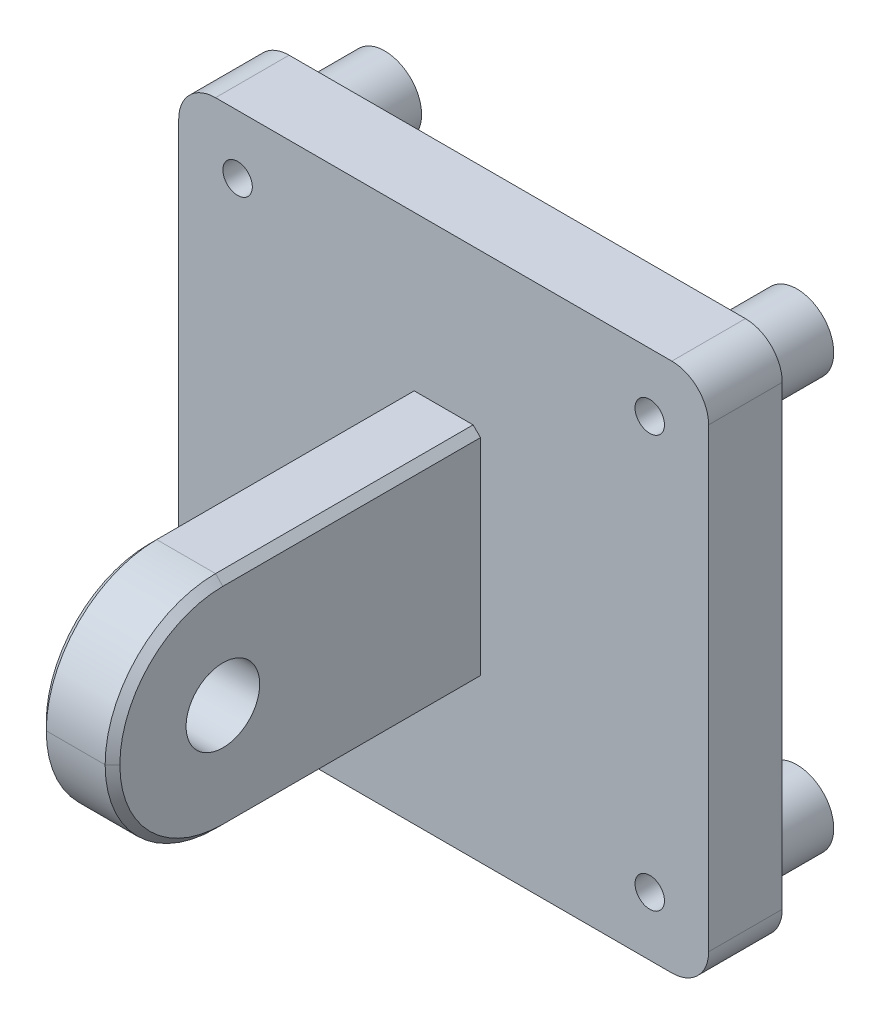
SolidWorks part; units mm, degrees
ref_plane "Front Plane" through (0, 0, 0) normal (0, 0, 1) x (1, 0, 0)
ref_plane "Top Plane" through (0, 0, 0) normal (0, 1, 0) x (1, 0, 0)
ref_plane "Right Plane" through (0, 0, 0) normal (1, 0, 0) x (0, 0, -1)
sketch "Sketch1" plane through (0, 0, 0) normal (0, 0, 1) x (1, 0, 0)
  line L1 (-18, -18) -> (18, -18)
  line L2 (-18, -18) -> (-18, 18)
  line L3 (-18, 18) -> (18, 18)
  line L4 (18, -18) -> (18, 18)
  line L5 (-14, -14) -> (14, -14)
  line L6 (-14, -14) -> (-14, 14)
  line L7 (-14, 14) -> (14, 14)
  line L8 (14, -14) -> (14, 14)
  line L9 (-14, -14) -> (14, 14) construction
  line L10 (-14, 14) -> (14, -14) construction
  circle A0 centre (-14, 14) radius 1
  circle A1 centre (14, 14) radius 1
  circle A2 centre (14, -14) radius 1
  circle A3 centre (-14, -14) radius 1
  circle A4 centre (-14, 14) radius 2.5
  circle A5 centre (14, 14) radius 2.5
  circle A6 centre (14, -14) radius 2.5
  circle A7 centre (-14, -14) radius 2.5
  point P4 (0, 0)
  dimension "D7" = 2
  dimension "D8" = 2
  dimension "D9" = 2
  dimension "D10" = 2
  dimension "D11" = 5
  dimension "D12" = 5
  dimension "D13" = 5
  dimension "D14" = 5
  dimension "D1" = 18
  dimension "D2" = 18
  dimension "D3" = 36
  dimension "D4" = 36
  dimension "D5" = 28
  dimension "D6" = 28
extrude "Boss-Extrude1" add sketch "Sketch1" against normal blind 5 contours L7 A4 L6 A0 | L6 A4 L7 A0 | L8 A5 L7 A1 | L7 A5 L8 A1 | L5 A7 L6 A3 | L6 A7 L5 A3 | L5 A6 L8 A2 | L8 A6 L5 A2 region at (-12.8177, -12.8177, 0) region at (-12.25, -14.0707, 0) region at (12.8177, -12.8177, 0) region at (12.25, -14.0707, 0) region at (-15.7178, 15.7178, 0) region at (-12.8177, 12.8177, 0) region at (12.8177, 12.8177, 0) region at (14.0707, 12.25, 0)
extrude "Boss-Extrude2" add sketch "Sketch1<3>" along normal blind 5 contours L1 L4 L3 L2 A7 L6 A4 L7 A5 L8 A6 L5 | A7 L5 A6 L8 A5 L7 A4 L6 | L6 A7 L5 A3 | L5 A7 L6 A3 | L7 A4 L6 A0 | L6 A4 L7 A0 | L8 A6 L5 A2 | L5 A6 L8 A2 | L7 A5 L8 A1 | L8 A5 L7 A1 region at (-17.4909, 0, 0) region at (-12.8177, -12.8177, 0) region at (-12.25, -14.0707, 0) region at (0, 0, 0) region at (12.8177, -12.8177, 0) region at (12.25, -14.0707, 0) region at (-15.7178, 15.7178, 0) region at (-12.8177, 12.8177, 0) region at (12.8177, 12.8177, 0) region at (14.0707, 12.25, 0)
sketch "Sketch1<3>" plane through (0, 0, 0) normal (0, 0, 1) x (1, 0, 0) same geometry as "Sketch1"
fillet "Fillet1" radius 2.5 4 edges at (18, 18, 2.5) (-18, 18, 2.5) (-18, -18, 2.5) (18, -18, 2.5)
sketch "Sketch2" plane through (0, 0, 5) normal (0, 0, 1) x (1, 0, 0)
  line L1 (-2.5, -7.5) -> (2.5, -7.5)
  line L2 (-2.5, -7.5) -> (-2.5, 7.5)
  line L3 (-2.5, 7.5) -> (2.5, 7.5)
  line L4 (2.5, -7.5) -> (2.5, 7.5)
  line L5 (-2.5, -7.5) -> (2.5, 7.5) construction
  line L6 (-2.5, 7.5) -> (2.5, -7.5) construction
  point P0 (0, 0)
  dimension "D1" = 5
  dimension "D2" = 15
extrude "Boss-Extrude3" add sketch "Sketch2" along normal blind 25
sketch "Sketch3" plane through (2.5, 0, 0) normal (1, 0, 0) x (0, 0, -1)
  line L0 (-30, -7.5) -> (-30, 7.5) construction
  line L1 (-30, 7.5) -> (-5, 7.5) construction
  circle A0 centre (-22.5, 0) radius 2.5
  dimension "D1" = 5
  dimension "D2" = 7.5
  dimension "D3" = 7.5
fillet "Fillet2" radius 7.5 2 edges at (0, -7.5, 30) (0, 7.5, 30)
extrude "Cut-Extrude1" cut sketch "Sketch3" against normal blind 5 contours A0
chamfer "Chamfer1" distance 0.5 angle 45 8 edges at (-2.5, 7.5, 13.75) (-2.5, 5.3033, 27.8033) (-2.5, -5.3033, 27.8033) (-2.5, -7.5, 13.75) (2.5, 7.5, 13.75) (2.5, 5.3033, 27.8033) (2.5, -7.5, 13.75) (2.5, -5.3033, 27.8033)
